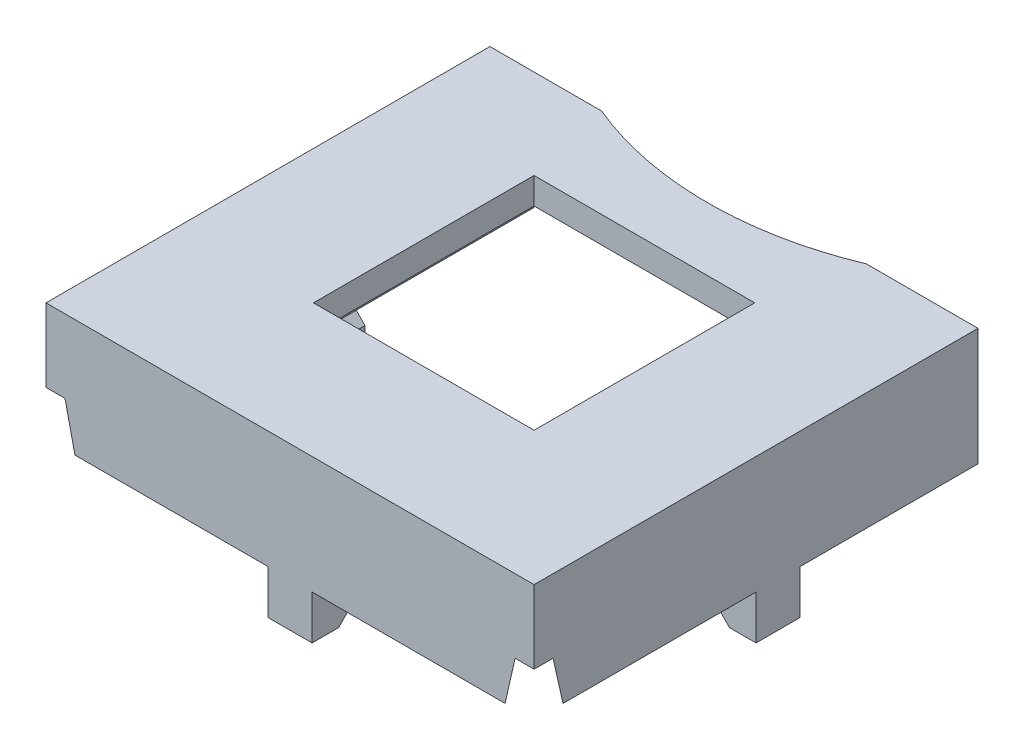
SolidWorks part; units mm, degrees
note: '?' marks a value the reader was unsure of. The reader was unsure of these and kept them because the rebuilt part matched: shared geometry of "Sketch1<3>".
ref_plane "Front Plane" through (0, 0, 0) normal (0, 0, 1) x (1, 0, 0)
ref_plane "Top Plane" through (0, 0, 0) normal (0, 1, 0) x (1, 0, 0)
ref_plane "Right Plane" through (0, 0, 0) normal (1, 0, 0) x (0, 0, -1)
sketch "Sketch1" plane through (0, 0, 0) normal (0, 1, 0) x (1, 0, 0)
  line L0 (-27.65, -27.65) -> (-27.65, 22.65)
  line L1 (-22.65, -22.65) -> (22.65, -22.65)
  line L2 (-22.65, -22.65) -> (-22.65, 22.65)
  line L3 (-22.65, 22.65) -> (22.65, 22.65)
  line L4 (22.65, -22.65) -> (22.65, 22.65)
  line L5 (-22.65, -22.65) -> (22.65, 22.65) construction
  line L6 (-22.65, 22.65) -> (22.65, -22.65) construction
  line L7 (-12.5, -12.5) -> (12.5, -12.5)
  line L8 (-12.5, -12.5) -> (-12.5, 12.5)
  line L9 (-12.5, 12.5) -> (12.5, 12.5)
  line L10 (12.5, -12.5) -> (12.5, 12.5)
  line L11 (-12.5, -12.5) -> (12.5, 12.5) construction
  line L12 (-12.5, 12.5) -> (12.5, -12.5) construction
  line L13 (-27.65, -27.65) -> (27.65, -27.65)
  line L14 (27.65, -27.65) -> (27.65, 22.65)
  line L15 (27.65, 22.65) -> (22.65, 22.65)
  line L16 (-27.65, 22.65) -> (-22.65, 22.65)
  point P0 (0, 0)
  point P5 (0, 0)
  dimension "D1" = 45.3
  dimension "D2" = 25
  dimension "D3" = 5
extrude "Boss-Extrude1" add sketch "Sketch1" along normal blind 3 contours L16 L0 L13 L14 L15 L4 L1 L2 | L1 L4 L3 L2 L10 L7 L8 L9
extrude "Boss-Extrude2" add sketch "Sketch1<3>" against normal blind 10.3 contours L16 L0 L13 L14 L15 L4 L1 L2
sketch "Sketch1<3>" plane through (0, 0, 0) normal (0, 1, 0) x (1, 0, 0) same geometry as "Sketch1"
ref_plane "Plane1" through (0, 0, 0) normal (0, 0, -1) x (-1, 0, 0)
sketch "Sketch2" plane through (0, 0, 0) normal (0, 0, -1) x (-1, 0, 0)
  line L3 (-21.65, -12.3) -> (-24.65, -15.3)
  line L4 (-24.65, -15.3) -> (-27.65, -15.3)
  line L5 (-27.65, -15.3) -> (-27.65, -10.3)
  line L7 (-27.65, -10.3) -> (-22.65, -10.3)
  line L8 (-22.65, -10.3) -> (-21.65, -11.3)
  line L9 (-21.65, -11.3) -> (-21.65, -12.3)
  dimension "D1" = 2
  dimension "D2" = 3
  dimension "D3" = 5
  dimension "D4" = 1
  dimension "D5" = 1
extrude "Boss-Extrude3" add sketch "Sketch2" along normal mid plane 5
ref_axis "Axis1" through (0, 0, 0) along (0, -1, 0)?
pattern_circular "CirPattern1" count 3 every 90 about axis through (0, 0, 0) along (0, 1, 0) of "Boss-Extrude3"
sketch "Sketch3" plane through (0, -10.3, 0) normal (0, -1, 0) x (1, 0, 0)
  line L0 (21.65, 22.65) -> (25.65, 27.65) construction
  line L1 (-22.65, 22.65) -> (22.65, 22.65) construction
  line L2 (-27.65, 27.65) -> (27.65, 27.65) construction
  line L3 (25.65, 27.65) -> (27.65, 27.65) construction
  line L4 (27.65, 27.65) -> (27.65, 25.65) construction
  line L5 (27.65, 27.65) -> (27.65, -22.65) construction
  line L6 (27.65, 25.65) -> (22.65, 21.65) construction
  line L7 (22.65, 22.65) -> (22.65, -22.65) construction
  line L8 (22.65, 21.65) -> (22.65, 22.65) construction
  line L9 (22.65, 22.65) -> (21.65, 22.65) construction
  line L10 (0, -1000) -> (0, 49000) construction
  line L17 (21.65, 21.65) -> (19.5694, 21.65)
  line L18 (19.5694, 21.65) -> (25.1694, 28.65)
  line L19 (25.1694, 28.65) -> (28.65, 28.65)
  line L20 (28.65, 28.65) -> (28.65, 25.1694)
  line L21 (28.65, 25.1694) -> (21.65, 19.5694)
  line L22 (21.65, 19.5694) -> (21.65, 21.65)
  line L23 (-21.65, 19.5694) -> (-21.65, 21.65)
  line L24 (-28.65, 25.1694) -> (-21.65, 19.5694)
  line L25 (-28.65, 28.65) -> (-28.65, 25.1694)
  line L26 (-25.1694, 28.65) -> (-28.65, 28.65)
  line L27 (-19.5694, 21.65) -> (-25.1694, 28.65)
  line L28 (-21.65, 21.65) -> (-19.5694, 21.65)
  dimension "D1" = 2
  dimension "D2" = 1
  dimension "D3" = 1
extrude "Cut-Extrude1" cut sketch "Sketch3" against normal blind 5 draft 10
sketch "Sketch5" plane through (0, 3, 0) normal (0, 1, 0) x (1, 0, 0)
  line L0 (-27.65, 22.65) -> (27.65, 22.65) construction
  line L1 (15, 22.65) -> (-15, 22.65)
  arc A0 (-15, 22.65) -> (15, 22.65) centre (0, 58.65) ccw
  point P3 (0, 19.65)
  dimension "D1" = 3
  dimension "D2" = 30
extrude "Cut-Extrude2" cut sketch "Sketch5" against normal up to next
